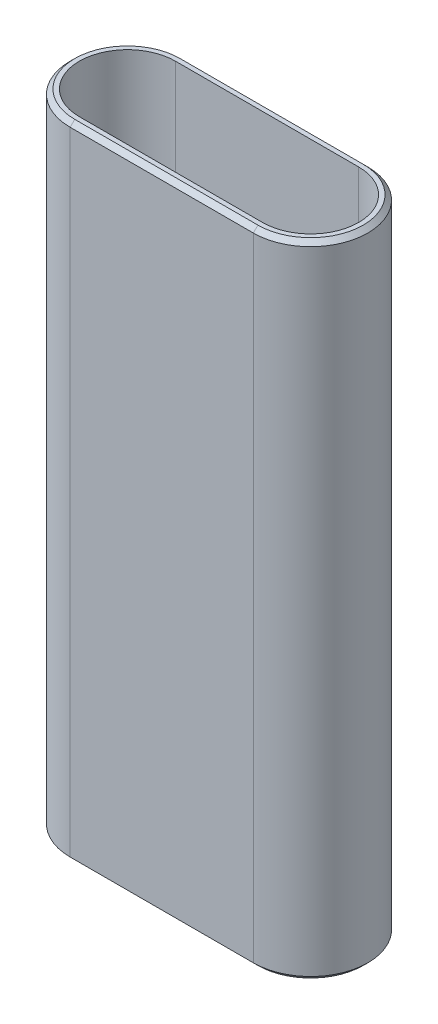
SolidWorks part; units mm, degrees
ref_plane "Front Plane" through (0, 0, 0) normal (0, 0, 1) x (1, 0, 0)
ref_plane "Top Plane" through (0, 0, 0) normal (0, 1, 0) x (1, 0, 0)
ref_plane "Right Plane" through (0, 0, 0) normal (1, 0, 0) x (0, 0, -1)
sketch "Sketch2" plane through (0, 12, 0) normal (0, -1, 0) x (1, 0, 0)
  line L8 (5.45, 3.45) -> (5.45, -3.45) construction
  line L9 (-7.45, -5.85) -> (7.45, -5.85)
  line L10 (-7.45, -5.85) -> (-7.45, 5.85)
  line L11 (-7.45, 5.85) -> (7.45, 5.85)
  line L12 (4.35, -3.85) -> (4.35, 3.85)
  line L13 (4.35, 3.85) -> (-4.35, 3.85)
  line L14 (-4.35, 3.85) -> (-4.35, -3.85)
  line L15 (-4.35, -3.85) -> (4.35, -3.85)
  line L16 (4.35, -3.85) -> (4.35, 3.85)
  line L17 (4.35, 3.85) -> (-4.35, 3.85)
  line L18 (-4.35, 3.85) -> (-4.35, -3.85)
  line L19 (-4.35, -3.85) -> (4.35, -3.85)
  line L20 (7.45, -5.85) -> (7.45, 5.85)
  line L21 (0, 5.85) -> (0, -5.85) construction
  line L22 (-7.45, 0) -> (7.45, 0) construction
  point P0 (0, 0)
  dimension "D2" = 2
  dimension "D3" = 2
  dimension "D1" = 0.4
extrude "Boss-Extrude1" add sketch "Sketch2" along normal offset from surface (12.6 mm away) 0.6 offset beyond the face yes
sketch "Sketch4" plane through (0, 0, 0) normal (1, 0, 0) x (0, 0, -1)
  line L1 (-1.6, 9.8) -> (-1.6, 8) construction
  line L2 (1.6, 8) -> (1.6, 9.8) construction
  line L3 (2.75, 8) -> (1.6, 8) construction
  line L4 (-1.6, 8) -> (-2.75, 8) construction
  line L5 (-2.75, 8) -> (-2.75, 12) construction
  line L6 (-2.75, 12) -> (-3.45, 12) construction
  line L7 (-3.45, 12) -> (-3.45, 0) construction
  line L8 (-3.45, 0) -> (3.45, 0) construction
  line L9 (3.45, 0) -> (3.45, 12) construction
  line L10 (3.45, 12) -> (2.75, 12) construction
  line L11 (2.75, 12) -> (2.75, 8) construction
  line L13 (-1.6, 9.8) -> (-1.6, 8) construction
  line L14 (1.6, 8) -> (1.6, 9.8) construction
  line L15 (2.75, 8) -> (1.6, 8) construction
  line L16 (-1.6, 8) -> (-2.75, 8) construction
  line L17 (-2.75, 8) -> (-2.75, 12) construction
  line L18 (-2.75, 12) -> (-3.45, 12) construction
  line L19 (-3.45, 12) -> (-3.45, 0) construction
  line L20 (-3.45, 0) -> (3.45, 0) construction
  line L21 (3.45, 0) -> (3.45, 12) construction
  line L22 (3.45, 12) -> (2.75, 12) construction
  line L23 (2.75, 12) -> (2.75, 8) construction
  line L24 (0, -990) -> (0, 49010) construction
  line L25 (-2.3, 10.25) -> (2.3, 10.25)
  line L26 (-2.3, 10.25) -> (-2.3, 7)
  line L27 (-2.3, 7) -> (2.3, 7)
  line L28 (1.6, 10) -> (-1.6, 10)
  line L29 (-1.6, 10) -> (-1.6, 9.8)
  line L30 (-1.6, 9.8) -> (1.6, 9.8)
  line L31 (1.6, 9.8) -> (1.6, 10)
  line L32 (1.6, 10) -> (-1.6, 10) construction
  line L33 (-1.6, 10) -> (-1.6, 9.8) construction
  line L34 (2.3, 10.25) -> (2.3, 7)
  line L35 (1.6, 9.8) -> (1.6, 10) construction
  point P20 (0, 10)
  dimension "D2" = 0.7
  dimension "D3" = 0.5
  dimension "D4" = 1
  dimension "D1" = 0
extrude "Cut-Extrude1" cut sketch "Sketch4" against normal through all both and the other way through all
sketch "Sketch5" plane through (0, -0.6, 0) normal (0, -1, 0) x (1, 0, 0)
  line L0 (-20, 0) -> (20, 0) construction
  line L1 (-20, 12.5) -> (20, 12.5)
  line L2 (-20, -12.5) -> (20, -12.5)
  arc A0 (-20, 12.5) -> (-20, -12.5) centre (-20, 0) ccw
  arc A1 (20, -12.5) -> (20, 12.5) centre (20, 0) ccw
  point P2 (0, 0)
  dimension "D1" = 25
  dimension "D2" = 40
extrude "Boss-Extrude2" add sketch "Sketch5" along normal blind 3
sketch "Sketch7" plane through (0, -0.6, 0) normal (0, 1, 0) x (1, 0, 0)
  line L0 (-20, -10.5) -> (20, -10.5)
  line L1 (20, 10.5) -> (-20, 10.5)
  line L2 (-20, -12.5) -> (20, -12.5)
  line L3 (20, 12.5) -> (-20, 12.5)
  line L4 (-20, -12.5) -> (20, -12.5)
  line L5 (20, 12.5) -> (-20, 12.5)
  arc A0 (20, -10.5) -> (20, 10.5) centre (20, 0) ccw
  arc A1 (-20, 10.5) -> (-20, -10.5) centre (-20, 0) ccw
  arc A2 (-20, 12.5) -> (-20, -12.5) centre (-20, 0) ccw
  arc A3 (20, -12.5) -> (20, 12.5) centre (20, 0) ccw
  arc A4 (-20, 12.5) -> (-20, -12.5) centre (-20, 0) ccw
  arc A5 (20, -12.5) -> (20, 12.5) centre (20, 0) ccw
  dimension "D1" = 0
  dimension "D2" = 2
extrude "Boss-Extrude3" add sketch "Sketch7" along normal blind 137
chamfer "Chamfer1" distance 1 angle 45 8 edges at (32.5, -3.6, 0) (0, -3.6, 12.5) (0, -3.6, -12.5) (-32.5, -3.6, 0) (32.5, 136.4, 0) (0, 136.4, -12.5) (0, 136.4, 12.5) (-32.5, 136.4, 0)
chamfer "Chamfer2" distance 0.8 angle 45 8 edges at (-7.45, 12, 0) (0, 12, -5.85) (7.45, 12, 0) (0, 12, 5.85) (0, 12, 3.85) (4.35, 12, 0) (0, 12, -3.85) (-4.35, 12, 0)
chamfer "Chamfer3" distance 2 angle 45 4 edges at (-7.45, 5.3, 5.85) (-7.45, 5.3, -5.85) (7.45, 5.3, -5.85) (7.45, 5.3, 5.85)
equation "\"case_length\"= 140"
equation "\"plate_thickness\"= 3"
equation "\"D1@Boss-Extrude2\"=\"plate_thickness\""
equation "\"D1@Boss-Extrude3\"=\"case_length\"-\"plate_thickness\""
equation "\"case_height\"= 25"
equation "\"case_width\"= 65"
equation "\"case_to_shell_offset\"= 19.6"
equation "\"body_tip_distance\"= 30"
equation "\"D2@Sketch5\"=\"case_width\"-\"case_height\""
equation "\"D1@Sketch5\"=\"case_height\""
